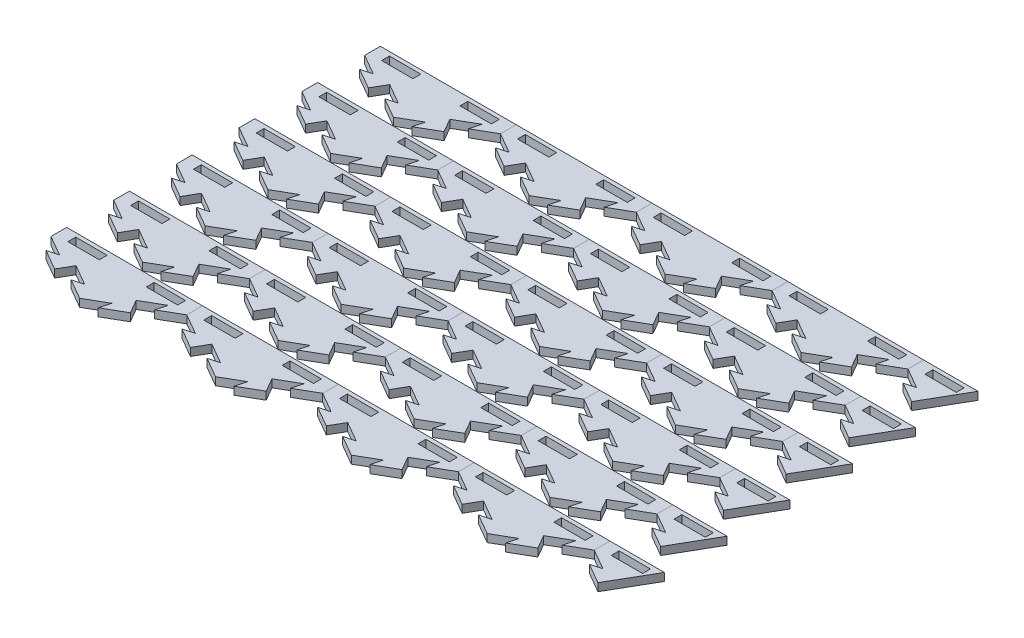
SolidWorks part; units mm, degrees
material "Cedar"
ref_plane "Front Plane" through (0, 0, 0) normal (0, 0, 1) x (1, 0, 0)
ref_plane "Top Plane" through (0, 0, 0) normal (0, 1, 0) x (1, 0, 0)
ref_plane "Right Plane" through (0, 0, 0) normal (1, 0, 0) x (0, 0, -1)
sketch "Sketch1" plane through (0, 0, 0) normal (0, 1, 0) x (1, 0, 0)
  line L0 (-54.9926, 0) -> (54.9926, 0) construction
  line L1 (-54.9926, 0) -> (0, -31.75)
  line L2 (0, -31.75) -> (54.9926, 0)
  line L3 (54.9926, 0) -> (54.9926, 63.5)
  line L4 (54.9926, 63.5) -> (0, 95.25)
  line L5 (0, 95.25) -> (-54.9926, 63.5)
  line L6 (-54.9926, 63.5) -> (-54.9926, 0)
  line L7 (0, -31.75) -> (0, 31.75) construction
  circle A0 centre (0, 31.75) radius 54.9926 construction
  point P9 (0, 0)
  dimension "D1" = 63.5
extrude "Boss-Extrude1" add sketch "Sketch1" against normal blind 6.35
sketch "Sketch2" plane through (0, 0, 0) normal (0, 1, 0) x (1, 0, 0)
  line L0 (-54.9926, 31.75) -> (54.9926, 31.75) construction
  line L1 (-54.9926, 63.5) -> (-54.9926, 0) construction
  line L2 (54.9926, 0) -> (54.9926, 63.5) construction
  point P2 (0, 31.75)
ref_axis "Axis1" through (0, 0, -31.75) along (0, 1, 0)
sketch "Sketch10" plane through (0, 0, 0) normal (0, 1, 0) x (1, 0, 0)
  line L0 (0, -31.75) -> (-16.4978, -22.225) construction
  line L1 (-16.4978, -22.225) -> (-7.8235, -19.9007)
  line L2 (-7.8235, -19.9007) -> (-24.3213, -10.3757)
  line L3 (-24.3213, -10.3757) -> (-27.4963, -15.875)
  line L4 (-16.4978, -22.225) -> (-27.4963, -15.875)
  line L5 (-54.9926, 0) -> (0, -31.75) construction
  dimension "D1" = 45
  dimension "D2" = 6.35
extrude "Cut-Extrude4" cut sketch "Sketch10" against normal through all
sketch "Sketch11" plane through (0, 0, 0) normal (0, 1, 0) x (1, 0, 0)
  line L0 (-27.4963, -15.875) -> (-54.9926, 0) construction
  line L1 (-27.4963, -15.875) -> (-30.6713, -21.3743)
  line L2 (-30.6713, -21.3743) -> (-47.1691, -11.8493)
  line L3 (-47.1691, -11.8493) -> (-38.4948, -9.525)
  line L4 (-38.4948, -9.525) -> (-27.4963, -15.875)
  line L5 (-38.4948, -9.525) -> (-54.9926, 0) construction
  line L6 (-38.4948, -9.525) -> (-54.9926, 0) construction
  line L7 (-54.9926, 0) -> (-27.4963, -15.875) construction
  line L8 (-54.9926, 63.5) -> (-54.9926, 0) construction
  dimension "D1" = 45
  dimension "D2" = 6.35
extrude "Boss-Extrude4" add sketch "Sketch11" against normal blind 6.35
pattern_circular "CirPattern1" count 2 every 60 about axis through (0, 0, -31.75) along (0, 1, 0) of "Cut-Extrude4", "Boss-Extrude4"
sketch "Sketch12" plane through (0, 0, 0) normal (0, 1, 0) x (1, 0, 0)
  line L0 (-54.9926, 12.7) -> (54.9926, 12.7)
  line L1 (-54.9926, 63.5) -> (-54.9926, 0) construction
  line L2 (54.9926, 0) -> (54.9926, 63.5) construction
  line L3 (54.9926, 12.7) -> (54.9926, 95.25)
  line L4 (54.9926, 95.25) -> (-54.9926, 95.25)
  line L5 (-54.9926, 95.25) -> (-54.9926, 12.7)
  line L6 (0, 0) -> (0, 12.7) construction
  dimension "D1" = 12.7
extrude "Cut-Extrude5" cut sketch "Sketch12" against normal through all
sketch "Sketch13" plane through (0, 0, 0) normal (0, 1, 0) x (1, 0, 0)
  line L0 (0, 0) -> (0, 12.7) construction
  line L1 (-54.9926, 12.7) -> (54.9926, 12.7) construction
  line L2 (-31.75, 6.35) -> (31.75, 6.35) construction
  line L4 (-44.45, 9.525) -> (-19.05, 9.525)
  line L5 (-44.45, 9.525) -> (-44.45, 3.175)
  line L6 (-44.45, 3.175) -> (-19.05, 3.175)
  line L7 (-19.05, 9.525) -> (-19.05, 3.175)
  line L8 (-44.45, 9.525) -> (-19.05, 3.175) construction
  line L9 (-44.45, 3.175) -> (-19.05, 9.525) construction
  line L10 (19.05, 9.525) -> (44.45, 9.525)
  line L11 (19.05, 9.525) -> (19.05, 3.175)
  line L12 (19.05, 3.175) -> (44.45, 3.175)
  line L13 (44.45, 9.525) -> (44.45, 3.175)
  line L14 (19.05, 9.525) -> (44.45, 3.175) construction
  line L15 (19.05, 3.175) -> (44.45, 9.525) construction
  point P7 (0, 6.35)
  point P8 (0, 6.35)
  dimension "D1" = 6.35
  dimension "D2" = 25.4
  dimension "D3" = 6.35
  dimension "D4" = 25.4
  dimension "D5" = 63.5
extrude "Cut-Extrude6" cut sketch "Sketch13" against normal through all
pattern_linear "LPattern1" count 5 spacing 109.9852 along (1, 0, 0) count 2 spacing 109.9852 along (-1, 0, 0) pattern seed only yes of bodies 136 131
sketch "Sketch14" plane through (0, 0, 0) normal (0, 1, 0) x (1, 0, 0)
  line L0 (439.9409, -31.75) -> (439.9409, 12.7)
  line L1 (384.9483, 12.7) -> (494.9335, 12.7) construction
  line L2 (439.9409, 12.7) -> (494.9335, 12.7)
  line L3 (494.9335, 12.7) -> (494.9335, -31.75)
  line L4 (494.9335, -31.75) -> (439.9409, -31.75)
  line L5 (-109.9852, -31.75) -> (-109.9852, 12.7)
  line L6 (-164.9778, 12.7) -> (-54.9926, 12.7) construction
  line L7 (-109.9852, 12.7) -> (-164.9778, 12.7)
  line L8 (-164.9778, 12.7) -> (-164.9778, -31.75)
  line L9 (-164.9778, -31.75) -> (-109.9852, -31.75)
  line L10 (415.6196, -10.3757) -> (428.9424, 12.7)
  line L11 (428.9424, 12.7) -> (439.9409, 12.7)
  line L12 (415.6196, -10.3757) -> (409.2696, -21.3743)
  line L13 (409.2696, -21.3743) -> (439.9409, -31.75)
  line L14 (-79.3139, -21.3743) -> (-98.9867, 12.7)
  line L15 (-98.9867, 12.7) -> (-109.9852, 12.7)
  line L16 (-79.3139, -21.3743) -> (-95.8117, -30.8993)
  line L17 (-95.8117, -30.8993) -> (-109.9852, -31.75)
  line L18 (-85.6639, -10.3757) -> (-79.3139, -21.3743) construction
  line M5 (484.3909, 9.525) -> (484.3909, 3.175)
  line M6 (484.3909, 3.175) -> (458.9909, 3.175)
  line M7 (458.9909, 3.175) -> (458.9909, 9.525)
  line M8 (458.9909, 9.525) -> (484.3909, 9.525)
  line M13 (494.9335, 12.7) -> (384.9483, 12.7)
  line M19 (415.6196, -10.3757) -> (432.1174, -19.9007)
  line M20 (432.1174, -19.9007) -> (423.4431, -22.225)
  line M21 (423.4431, -22.225) -> (439.9409, -31.75)
  line M22 (439.9409, -31.75) -> (456.4387, -22.225)
  line M23 (456.4387, -22.225) -> (454.1144, -30.8993)
  line M24 (454.1144, -30.8993) -> (470.6122, -21.3743)
  line M25 (470.6122, -21.3743) -> (464.2622, -10.3757)
  line M26 (464.2622, -10.3757) -> (480.76, -0.8507)
  line M27 (480.76, -0.8507) -> (478.4357, -9.525)
  line M28 (478.4357, -9.525) -> (494.9335, 0)
  line M29 (494.9335, 0) -> (494.9335, 12.7)
extrude "Cut-Extrude7" cut sketch "Sketch14" against normal through all contours L17 L16 L14 L15 L5 | L10 L0 M19 M20 M21 M13 | L0 M22 M23 M24 M25 M26 M27 M28 M29 M13 M8 M5 M6 M7 | L8 L9 L5 L7 region at (431.3731, 0, 7.3494) region at (460.5225, 0, 5.1278) region at (-137.4815, 0, 9.525) region at (-98.715, 0, 11.4335)
sketch "Sketch15" plane through (0, 0, 0) normal (0, 1, 0) x (1, 0, 0)
  line L0 (-98.9867, 12.7) -> (-54.9926, 12.7)
  line L1 (-54.9926, 12.7) -> (-54.9926, -10.3757)
  line L2 (-54.9926, -10.3757) -> (-98.9867, -10.3757)
  line L3 (-98.9867, -10.3757) -> (-98.9867, 12.7)
extrude "Cut-Extrude8" cut sketch "Sketch15" against normal through all
pattern_linear "LPattern2" count 6 spacing 50.8 along (0, 0, 1) of bodies 144 134 133 132 136
